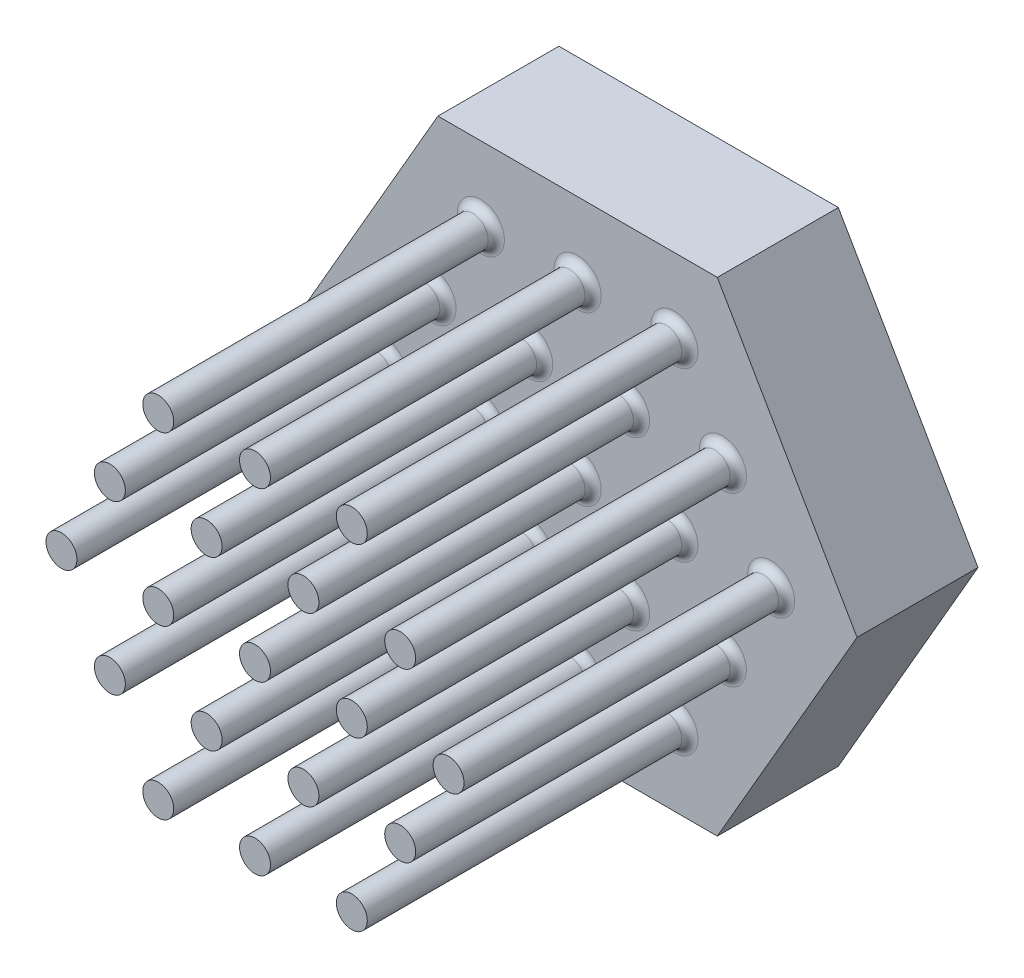
SolidWorks part; units mm, degrees
note: The reader was unsure of these and kept them because the rebuilt part matched: shared geometry of "Sketch1<3>".
ref_plane "Front Plane" through (0, 0, 0) normal (0, 0, 1) x (1, 0, 0)
ref_plane "Top Plane" through (0, 0, 0) normal (0, 1, 0) x (1, 0, 0)
ref_plane "Right Plane" through (0, 0, 0) normal (1, 0, 0) x (0, 0, -1)
sketch "Sketch1" plane through (0, 0, 0) normal (0, 0, 1) x (1, 0, 0)
  line L1 (6.9282, 0) -> (3.4641, 6)
  line L2 (3.4641, 6) -> (-3.4641, 6)
  line L3 (-3.4641, 6) -> (-6.9282, 0)
  line L4 (-6.9282, 0) -> (-3.4641, -6)
  line L5 (-3.4641, -6) -> (3.4641, -6)
  line L6 (3.4641, -6) -> (6.9282, 0)
  circle A1 centre (0, 0) radius 0.384
  circle A2 centre (2.4, 0) radius 0.384
  circle A3 centre (4.8, 0) radius 0.384
  circle A4 centre (-2.4, 0) radius 0.384
  circle A5 centre (-4.8, 0) radius 0.384
  circle A6 centre (1.2, 2.0785) radius 0.384
  circle A7 centre (3.6, 2.0785) radius 0.384
  circle A9 centre (-1.2, 2.0785) radius 0.384
  circle A10 centre (-3.6, 2.0785) radius 0.384
  circle A11 centre (2.4, 4.1569) radius 0.384
  circle A14 centre (0, 4.1569) radius 0.384
  circle A15 centre (-2.4, 4.1569) radius 0.384
  circle A16 centre (-1.2, -2.0785) radius 0.384
  circle A17 centre (1.2, -2.0785) radius 0.384
  circle A18 centre (3.6, -2.0785) radius 0.384
  circle A19 centre (-3.6, -2.0785) radius 0.384
  circle A21 centre (-2.4, -4.1569) radius 0.384
  circle A22 centre (0, -4.1569) radius 0.384
  circle A23 centre (2.4, -4.1569) radius 0.384
  circle A26 centre (7.2, 4.1569) radius 0.384 [skipped]
  circle A27 centre (6, 2.0785) radius 0.384 [skipped]
  circle A28 centre (4.8, 4.1569) radius 0.384 [skipped]
  circle A29 centre (-6, -2.0785) radius 0.384 [skipped]
  circle A30 centre (-4.8, -4.1569) radius 0.384 [skipped]
  circle A31 centre (-7.2, -4.1569) radius 0.384 [skipped]
  dimension "D1" = 3
  dimension "D5" = 1.2
  dimension "D6" = 2.4
  dimension "D2" = 3
  dimension "D3" = 3
  dimension "D4" = 3
extrude "Boss-Extrude1" add sketch "Sketch1" along normal blind 8 contours A3 | A7 | A11 | A14 | A15 | A10 | A9 | A6 | A2 | A18 | A17 | A1 | A4 | A5 | A19 | A16 | A23 | A22 | A21
extrude "Boss-Extrude2" add sketch "Sketch1<3>" against normal blind 3 contours L5 L6 L1 L2 L3 L4 A23 A22 A21 A19 A18 A17 A16 A15 A14 A11 A10 A9 A7 A6 A5 A4 A3 A2 A1 | A18 | A3 | A7 | A11 | A14 | A2 | A6 | A23 | A17 | A1 | A9 | A15 | A10 | A4 | A16 | A22 | A21 | A19 | A5
sketch "Sketch1<3>" plane through (0, 0, 0) normal (0, 0, 1) x (1, 0, 0) same geometry as "Sketch1"
fillet "Fillet1" radius 0.2 19 edges at (0.384, 4.1569, 0) (-2.016, 4.1569, 0) (-0.816, 2.0785, 0) (-2.016, 0, 0) (-3.216, 2.0785, 0) (-4.416, 0, 0) (-3.216, -2.0785, 0) (-2.016, -4.1569, 0) (0.384, -4.1569, 0) (-0.816, -2.0785, 0) (2.784, -4.1569, 0) (1.584, -2.0785, 0) (0.384, 0, 0) (1.584, 2.0785, 0) (2.784, 4.1569, 0) (3.984, 2.0785, 0) (3.984, -2.0785, 0) (2.784, 0, 0) (5.184, 0, 0)
